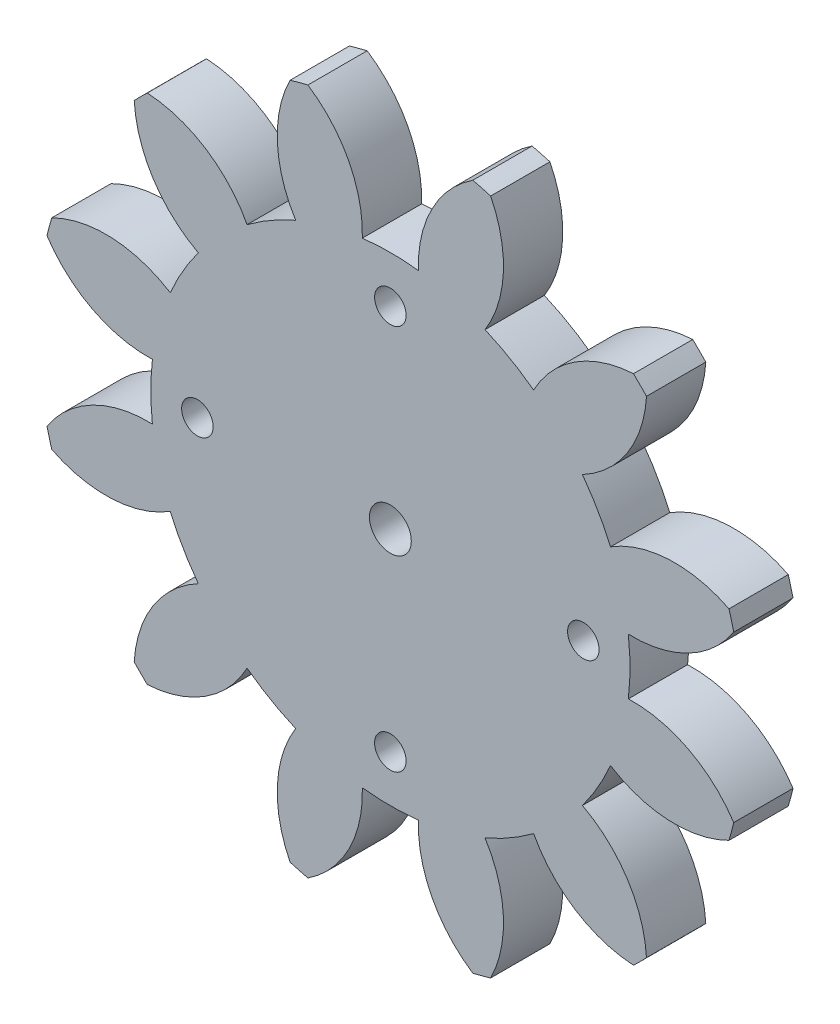
SolidWorks part; units mm, degrees
ref_plane "Front Plane" through (0, 0, 0) normal (0, 0, 1) x (1, 0, 0)
ref_plane "Top Plane" through (0, 0, 0) normal (0, 1, 0) x (1, 0, 0)
ref_plane "Right Plane" through (0, 0, 0) normal (1, 0, 0) x (0, 0, -1)
sketch "Sketch1" plane through (0, 0, 0) normal (0, 0, 1) x (1, 0, 0)
  arc A0 (31.0892, -0.0096) -> (27.1315, -2.5505) centre (31.371, -4.8013) ccw
  arc A1 (27.1315, -2.5505) -> (25.2056, -1.4386) centre (21.4517, -10.1644) ccw
  arc A2 (25.2056, -1.4386) -> (25.4272, 3.2593) centre (21.1366, 1.1075) ccw
  arc A3 (25.4272, 3.2593) -> (24.7206, 3.4487) centre (21.4517, -10.1644) ccw
  arc A4 (24.7206, 3.4487) -> (22.5636, -0.7307) centre (27.3606, -0.5602) ccw
  arc A5 (22.5636, -0.7307) -> (20.3398, -0.7307) centre (21.4517, -10.1644) ccw
  arc A6 (20.3398, -0.7307) -> (18.1828, 3.4487) centre (15.5428, -0.5602) ccw
  arc A7 (18.1828, 3.4487) -> (17.4762, 3.2593) centre (21.4517, -10.1644) ccw
  arc A8 (17.4762, 3.2593) -> (17.6978, -1.4386) centre (21.7669, 1.1075) ccw
  arc A9 (17.6978, -1.4386) -> (15.7719, -2.5505) centre (21.4517, -10.1644) ccw
  arc A10 (15.7719, -2.5505) -> (11.8142, -0.0096) centre (11.5324, -4.8013) ccw
  arc A11 (11.8142, -0.0096) -> (11.297, -0.5269) centre (21.4517, -10.1644) ccw
  arc A12 (11.297, -0.5269) -> (13.8378, -4.4846) centre (16.0887, -0.245) ccw
  arc A13 (13.8378, -4.4846) -> (12.7259, -6.4104) centre (21.4517, -10.1644) ccw
  arc A14 (12.7259, -6.4104) -> (8.028, -6.1888) centre (10.1798, -10.4795) ccw
  arc A15 (8.028, -6.1888) -> (7.8387, -6.8954) centre (21.4517, -10.1644) ccw
  arc A16 (7.8387, -6.8954) -> (12.018, -9.0524) centre (11.8475, -4.2555) ccw
  arc A17 (12.018, -9.0524) -> (12.018, -11.2763) centre (21.4517, -10.1644) ccw
  arc A18 (12.018, -11.2763) -> (7.8387, -13.4333) centre (11.8475, -16.0732) ccw
  arc A19 (7.8387, -13.4333) -> (8.028, -14.1399) centre (21.4517, -10.1644) ccw
  arc A20 (8.028, -14.1399) -> (12.7259, -13.9183) centre (10.1798, -9.8492) ccw
  arc A21 (12.7259, -13.9183) -> (13.8378, -15.8441) centre (21.4517, -10.1644) ccw
  arc A22 (13.8378, -15.8441) -> (11.297, -19.8018) centre (16.0887, -20.0837) ccw
  arc A23 (11.297, -19.8018) -> (11.8142, -20.3191) centre (21.4517, -10.1644) ccw
  arc A24 (11.8142, -20.3191) -> (15.7719, -17.7782) centre (11.5324, -15.5274) ccw
  arc A25 (15.7719, -17.7782) -> (17.6978, -18.8901) centre (21.4517, -10.1644) ccw
  arc A26 (17.6978, -18.8901) -> (17.4762, -23.588) centre (21.7669, -21.4363) ccw
  arc A27 (17.4762, -23.588) -> (18.1828, -23.7774) centre (21.4517, -10.1644) ccw
  arc A28 (18.1828, -23.7774) -> (20.3398, -19.5981) centre (15.5428, -19.7685) ccw
  arc A29 (20.3398, -19.5981) -> (22.5636, -19.5981) centre (21.4517, -10.1644) ccw
  arc A30 (22.5636, -19.5981) -> (24.7206, -23.7774) centre (27.3606, -19.7685) ccw
  arc A31 (24.7206, -23.7774) -> (25.4272, -23.588) centre (21.4517, -10.1644) ccw
  arc A32 (25.4272, -23.588) -> (25.2056, -18.8901) centre (21.1366, -21.4363) ccw
  arc A33 (25.2056, -18.8901) -> (27.1315, -17.7782) centre (21.4517, -10.1644) ccw
  arc A34 (27.1315, -17.7782) -> (31.0892, -20.3191) centre (31.371, -15.5274) ccw
  arc A35 (31.0892, -20.3191) -> (31.6064, -19.8018) centre (21.4517, -10.1644) ccw
  arc A36 (31.6064, -19.8018) -> (29.0656, -15.8441) centre (26.8147, -20.0837) ccw
  arc A37 (29.0656, -15.8441) -> (30.1775, -13.9183) centre (21.4517, -10.1644) ccw
  arc A38 (30.1775, -13.9183) -> (34.8754, -14.1399) centre (32.7236, -9.8492) ccw
  arc A39 (34.8754, -14.1399) -> (35.0647, -13.4333) centre (21.4517, -10.1644) ccw
  arc A40 (35.0647, -13.4333) -> (30.8854, -11.2763) centre (31.0559, -16.0732) ccw
  arc A41 (30.8854, -11.2763) -> (30.8854, -9.0524) centre (21.4517, -10.1644) ccw
  arc A42 (30.8854, -9.0524) -> (35.0647, -6.8954) centre (31.0559, -4.2555) ccw
  arc A43 (35.0647, -6.8954) -> (34.8754, -6.1888) centre (21.4517, -10.1644) ccw
  arc A44 (34.8754, -6.1888) -> (30.1775, -6.4104) centre (32.7236, -10.4795) ccw
  arc A45 (30.1775, -6.4104) -> (29.0656, -4.4846) centre (21.4517, -10.1644) ccw
  arc A46 (29.0656, -4.4846) -> (31.6064, -0.5269) centre (26.8147, -0.245) ccw
  arc A47 (31.6064, -0.5269) -> (31.0892, -0.0096) centre (21.4517, -10.1644) ccw
  circle A48 centre (21.4517, -10.1644) radius 0.83
  dimension "D1" = 1.66
extrude "Boss-Extrude1" add sketch "Sketch1" along normal blind 2.35
sketch "Sketch2" plane through (0, 0, 2.35) normal (0, 0, 1) x (1, 0, 0)
  line L0 (21.4517, -10.1644) -> (21.4517, 3.7106) construction
  circle A0 centre (21.4517, -2.5144) radius 0.625
  dimension "D1" = 1.25
  dimension "D2" = 7.65
extrude "Cut-Extrude1" cut sketch "Sketch2" against normal blind 10
sketch "Sketch4" plane through (0, 0, 2.35) normal (0, 0, 1) x (1, 0, 0)
  line L0 (21.4517, -19.6634) -> (21.4517, -0.6654) construction
  line L1 (11.9527, -10.1644) -> (30.9507, -10.1644) construction
  arc A0 (12.018, -9.0524) -> (12.018, -11.2763) centre (21.4517, -10.1644) ccw construction
  arc A1 (30.8854, -11.2763) -> (30.8854, -9.0524) centre (21.4517, -10.1644) ccw construction
  arc A2 (20.3398, -19.5981) -> (22.5636, -19.5981) centre (21.4517, -10.1644) ccw construction
  arc A3 (22.5636, -0.7307) -> (20.3398, -0.7307) centre (21.4517, -10.1644) ccw construction
ref_plane "Plane1" through (0, -10.1644, 0) normal (0, -1, 0) x (-1, 0, 0)
ref_plane "Plane2" through (21.4517, 0, 0) normal (1, 0, 0) x (0, 0, -1)
ref_axis "Axis1" through (21.4517, -10.1644, 17.3243) along (0, 0, -1)
pattern_circular "CirPattern1" count 4 over 360 about axis through (21.4517, -10.1644, 17.3243) along (0, 0, -1) of "Cut-Extrude1"
